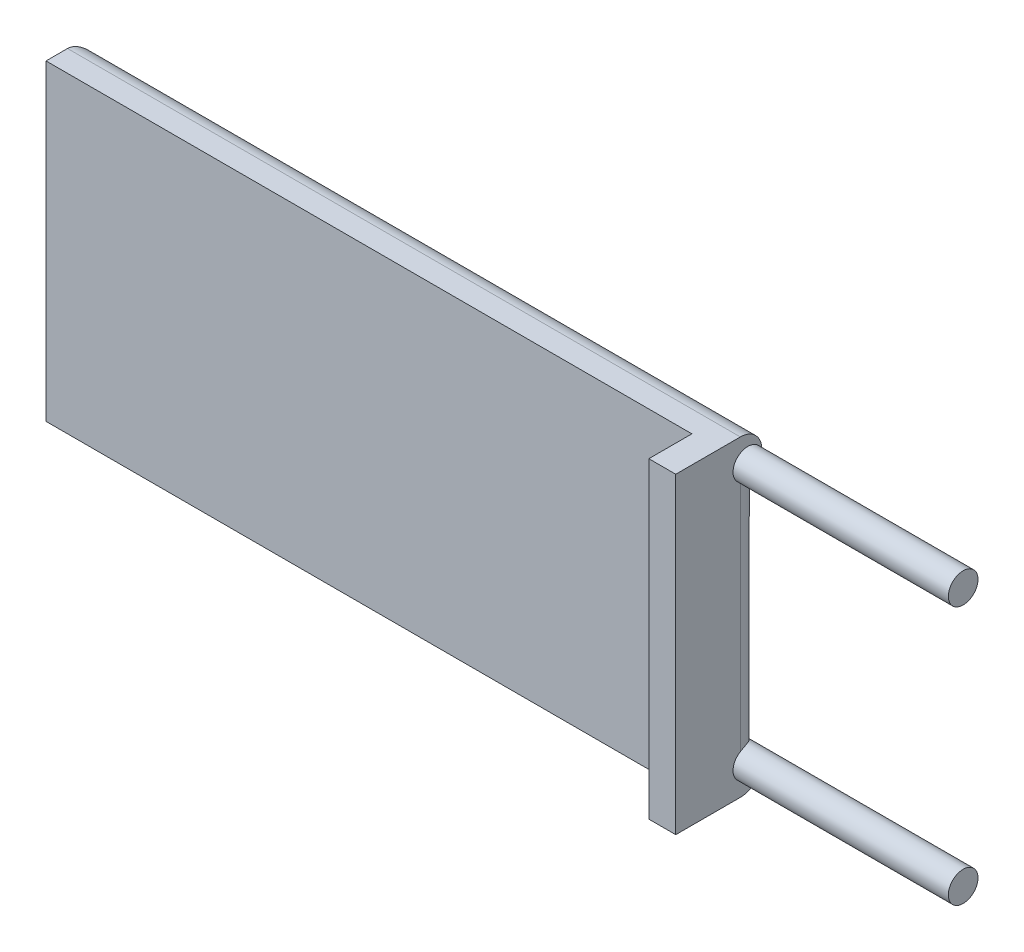
SolidWorks part; units mm, degrees
material "Beryllium Copper, UNS C17000"
ref_plane "Front Plane" through (0, 0, 0) normal (0, 0, 1) x (1, 0, 0)
ref_plane "Top Plane" through (0, 0, 0) normal (0, 1, 0) x (1, 0, 0)
ref_plane "Right Plane" through (0, 0, 0) normal (1, 0, 0) x (0, 0, -1)
sketch "Sketch1" plane through (0, 0, 0) normal (0, 0, 1) x (1, 0, 0)
  line L1 (38.1, -18.415) -> (-38.1, -18.415)
  line L2 (38.1, -18.415) -> (38.1, 18.415)
  line L3 (38.1, 18.415) -> (-38.1, 18.415)
  line L4 (-38.1, -18.415) -> (-38.1, 18.415)
  line L5 (38.1, -18.415) -> (-38.1, 18.415) construction
  line L6 (38.1, 18.415) -> (-38.1, -18.415) construction
  point P0 (0, 0)
  dimension "D1" = 76.2
  dimension "D2" = 36.83
extrude "Boss-Extrude1" add sketch "Sketch1" along normal blind 5.08
sketch "Sketch2" plane through (38.1, 0, 0) normal (1, 0, 0) x (0, 0, -1)
  line L0 (-5.08, -18.415) -> (-5.08, 18.415) construction
  line L1 (-10.16, -18.415) -> (0, -18.415)
  line L2 (-10.16, -18.415) -> (-10.16, 18.415)
  line L3 (-10.16, 18.415) -> (0, 18.415)
  line L4 (0, -18.415) -> (0, 18.415)
  line L5 (-10.16, -18.415) -> (0, 18.415) construction
  line L6 (-10.16, 18.415) -> (0, -18.415) construction
  point P0 (-5.08, 0)
extrude "Boss-Extrude2" add sketch "Sketch2" along normal blind 3.175
sketch "Sketch3" plane through (41.275, 0, 0) normal (1, 0, 0) x (0, 0, -1)
  line L0 (0, -18.415) -> (0, 18.415) construction
  line L1 (-9.4828, 0) -> (6.7556, 0) construction
  circle A0 centre (-1.651, 15.25) radius 1.75
  circle A1 centre (-1.651, -15.25) radius 1.75
  dimension "D3" = 3.5
  dimension "D1" = 15.25
  dimension "D2" = 1.651
extrude "Boss-Extrude3" add sketch "Sketch3" along normal blind 25.4
fillet "Fillet1" radius 2.54 4 edges at (1.5875, 18.415, 0) (1.5875, -18.415, 0) (41.275, 0, 0) (-38.1, 0, 0)
